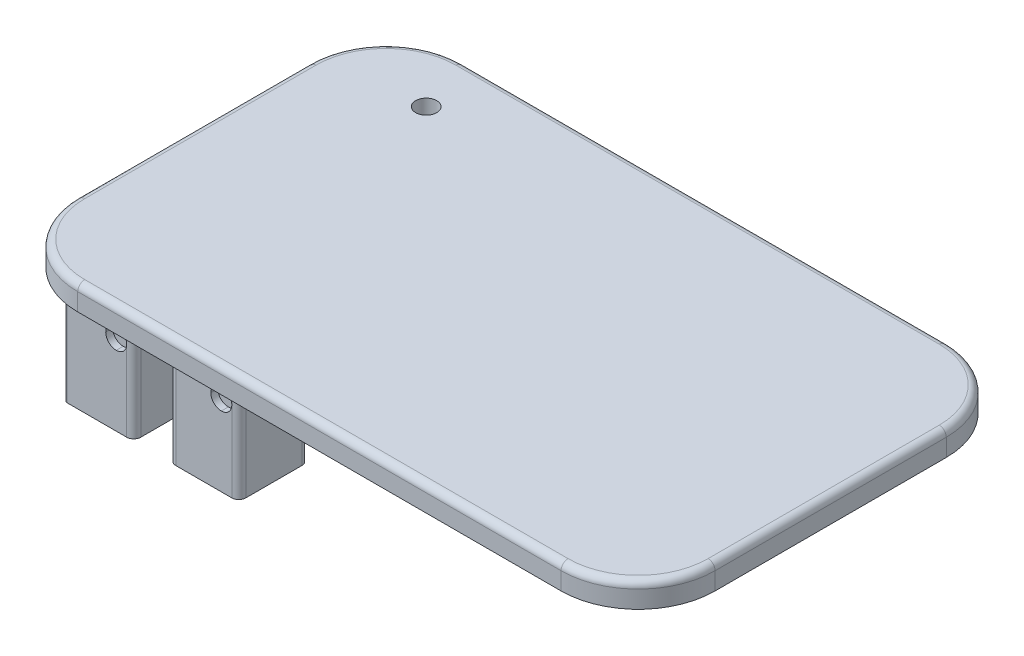
SolidWorks part; units mm, degrees
material "Custom Plastic"
ref_plane "Front Plane" through (0, 0, 0) normal (0, 0, 1) x (1, 0, 0)
ref_plane "Top Plane" through (0, 0, 0) normal (0, 1, 0) x (1, 0, 0)
ref_plane "Right Plane" through (0, 0, 0) normal (1, 0, 0) x (0, 0, -1)
sketch "Sketch1" plane through (0, 0, 0) normal (0, 1, 0) x (1, 0, 0)
  line L0 (-45.5, 27.5) -> (45.5, -27.5) construction
  line L1 (-45.5, -27.5) -> (45.5, -27.5)
  line L2 (-45.5, -27.5) -> (-45.5, 27.5)
  line L3 (-45.5, 27.5) -> (45.5, 27.5)
  line L4 (45.5, -27.5) -> (45.5, 27.5)
  point P4 (0, 0)
  dimension "D1" = 91
  dimension "D2" = 55
extrude "Boss-Extrude1" add sketch "Sketch1" along normal blind 3.5
fillet "Fillet1" radius 11 4 edges at (-45.5, 1.75, 27.5) (-45.5, 1.75, -27.5) (45.5, 1.75, -27.5) (45.5, 1.75, 27.5)
sketch "Sketch2" plane through (0, 3.5, 0) normal (0, 1, 0) x (1, 0, 0)
  line L0 (-36.5, -25.5) -> (-28.5, -17.5) construction
  line L1 (-37.5, -16.5) -> (-27.5, -16.5)
  line L2 (-37.5, -16.5) -> (-37.5, -26.5)
  line L3 (-37.5, -26.5) -> (-27.5, -26.5)
  line L4 (-27.5, -16.5) -> (-27.5, -26.5)
  line L5 (-36.5, -17.5) -> (-28.5, -17.5)
  line L6 (-36.5, -17.5) -> (-36.5, -25.5)
  line L7 (-36.5, -25.5) -> (-28.5, -25.5)
  line L8 (-28.5, -17.5) -> (-28.5, -25.5)
  line L9 (-37.5, -16.5) -> (-27.5, -26.5) construction
  line L11 (-45.5, 16.5) -> (-45.5, -16.5) construction
  line L12 (-32.5, -19.5) -> (-32.5, -23.5) construction
  line L13 (-34.5, -23.5) -> (-30.5, -23.5)
  line L14 (-34.5, -23.5) -> (-34.5, -19.5)
  line L15 (-34.5, -19.5) -> (-30.5, -19.5)
  line L16 (-30.5, -23.5) -> (-30.5, -19.5)
  line L17 (-34.5, -27.5) -> (34.5, -27.5) construction
  point P8 (-32.5, -21.5)
  point P9 (-32.5, -21.5)
  point P20 (-32.5, -21.5)
  dimension "D1" = 1
  dimension "D2" = 10
  dimension "D3" = 1
  dimension "D4" = 8
  dimension "D5" = 4
extrude "Boss-Extrude2" add sketch "Sketch2" against normal blind 13 from surface contours L4 L1 L2 L3 L5 L8 L7 L6 | L13 L16 L15 L14 region at (-32.5, 3.5, 16.6414) region at (-32.5, 3.5, 21.5) starting at face at (0, 0, 0)
sketch "Sketch3" plane through (0, -13, 0) normal (0, -1, 0) x (-1, 0, 0)
  line L0 (37.5, -16.5) -> (37.5, -26.5) construction
  line L1 (36.5, -25.5) -> (37.5, -25.5)
  line L2 (36.5, -25.5) -> (36.5, -22.5)
  line L3 (36.5, -22.5) -> (37.5, -22.5)
  line L4 (37.5, -25.5) -> (37.5, -22.5)
  line L5 (27.5, -26.5) -> (37.5, -26.5) construction
  line L6 (31.5, -25.5) -> (28.5, -25.5)
  line L7 (31.5, -25.5) -> (31.5, -26.5)
  line L8 (31.5, -26.5) -> (28.5, -26.5)
  line L9 (28.5, -25.5) -> (28.5, -26.5)
  dimension "D1" = 3
  dimension "D2" = 3
extrude "Cut-Extrude1" cut sketch "Sketch3" against normal blind 3 from offset 10 offset against normal yes
fillet "Fillet2" radius 1.4999 6 edges at (-28.5, -3, 26) (-31.5, -3, 26) (-28.5, 0, 22) (-31.5, 0, 26) (-37, -3, 25.5) (-37, -3, 22.5)
pattern_linear "LPattern1" count 2 spacing 15 along (1, 0, 0) of "Cut-Extrude1", "Boss-Extrude2", "Fillet2"
fillet "Fillet3" radius 0.5 1 edges at (-37.5, -6.5, 26.5)
sketch "Sketch4" plane through (0, 0, 0) normal (0, -1, 0) x (1, 0, 0)
  line L0 (-6.86, 1.61) -> (34.64, 1.61) construction
  line L1 (34.64, 1.61) -> (34.64, 17.51) construction
  line L2 (34.64, 17.51) -> (-6.86, 17.51) construction
  line L3 (-6.86, 17.51) -> (-6.86, 1.61) construction
  line L4 (-34.5, 27.5) -> (34.5, 27.5) construction
  line L5 (45.5, 16.5) -> (45.5, -16.5) construction
  circle A0 centre (-6.86, 17.51) radius 0.75
  circle A1 centre (34.64, 17.51) radius 0.75
  circle A2 centre (34.64, 1.61) radius 0.75
  circle A3 centre (-6.86, 1.61) radius 0.75
  circle A4 centre (34.64, 1.61) radius 1.75
  circle A5 centre (34.64, 17.51) radius 1.75
  circle A6 centre (-6.86, 17.51) radius 1.75
  circle A7 centre (-6.86, 1.61) radius 1.75
  dimension "D1" = 1.5
  dimension "D2" = 9.99
  dimension "D3" = 10.86
  dimension "D4" = 15.9
  dimension "D5" = 41.5
  dimension "D6" = 1
extrude "Boss-Extrude3" add sketch "Sketch4" along normal blind 1.5
extrude "Cut-Extrude2" cut sketch "Sketch4<2>" against normal blind 3 contours A3 | A0 | A1 | A2 region at (-6.86, 0, 17.51) region at (34.64, 0, 17.51) region at (34.64, 0, 1.61) region at (-6.86, 0, 1.61)
sketch "Sketch4<2>" plane through (0, 0, 0) normal (0, -1, 0) x (1, 0, 0) same geometry as "Sketch4"
fillet "Fillet4" radius 1 27 edges at (-28.5, -7.2501, 25.5) (-30.5, -6.5, 23.5) (-34.5, -6.5, 23.5) (-36.5, -7.2501, 25.5) (-27.5, -6.5, 26.5) (-12.5, -6.5, 26.5) (-22.5, -6.5, 26.5) (-21.5, -7.2501, 25.5) (-15.5, -6.5, 23.5) (-19.5, -6.5, 23.5) (-13.5, -7.2501, 25.5) (-13.5, -7.25, 17.5) (-12.5, -6.5, 16.5) (-15.5, -6.5, 19.5) (-19.5, -6.5, 19.5) (-21.5, -6.5, 17.5) (-22.5, -6.5, 16.5) (-28.5, -7.25, 17.5) (-27.5, -6.5, 16.5) (-30.5, -6.5, 19.5) (-34.5, -6.5, 19.5) (-36.5, -6.5, 17.5) (-37.5, -6.5, 16.5) (-18.25, 0, 17.5) (-13.9393, -0.4393, 17.5) (-33.2499, 0, 17.5) (-28.9393, -0.4393, 17.5)
sketch "Sketch5" plane through (0, 0, 0) normal (0, -1, 0) x (1, 0, 0)
  line L0 (34.5, -27.5) -> (-34.5, -27.5) construction
  line L1 (-45.5, -16.5) -> (-45.5, 16.5) construction
  circle A0 centre (-31.5, -19.25) radius 1.5
  dimension "D1" = 3
  dimension "D2" = 8.25
  dimension "D3" = 14
extrude "Cut-Extrude3" cut sketch "Sketch5" against normal through all
sketch "Sketch6" plane through (0, 0, 0) normal (0, -1, 0) x (1, 0, 0)
  line L0 (-45.5, -16.5) -> (-45.5, 16.5) construction
  line L1 (-37.9, -16.7395) -> (-12.5, -16.7395)
  line L2 (-37.9, -16.7395) -> (-37.9, 15.0105)
  line L3 (-37.9, 15.0105) -> (-12.5, 15.0105)
  line L4 (-12.5, -16.7395) -> (-12.5, 15.0105)
  line L5 (34.5, -27.5) -> (-34.5, -27.5) construction
  dimension "D1" = 31.75
  dimension "D2" = 25.4
  dimension "D3" = 7.6
  dimension "D4" = 10.7605
extrude "Cut-Extrude4" cut sketch "Sketch6" against normal blind 3
fillet "Fillet5" radius 0.5 4 edges at (-25.2, 3, 15.0105) (-12.5, 3, -0.8645) (-25.2, 3, -16.7395) (-37.9, 3, -0.8645)
fillet "Fillet6" radius 1 8 edges at (42.2782, 3.5, -24.2782) (45.5, 3.5, 0) (42.2782, 3.5, 24.2782) (0, 3.5, 27.5) (-42.2782, 3.5, 24.2782) (-45.5, 3.5, 0) (-42.2782, 3.5, -24.2782) (0, 3.5, -27.5)
